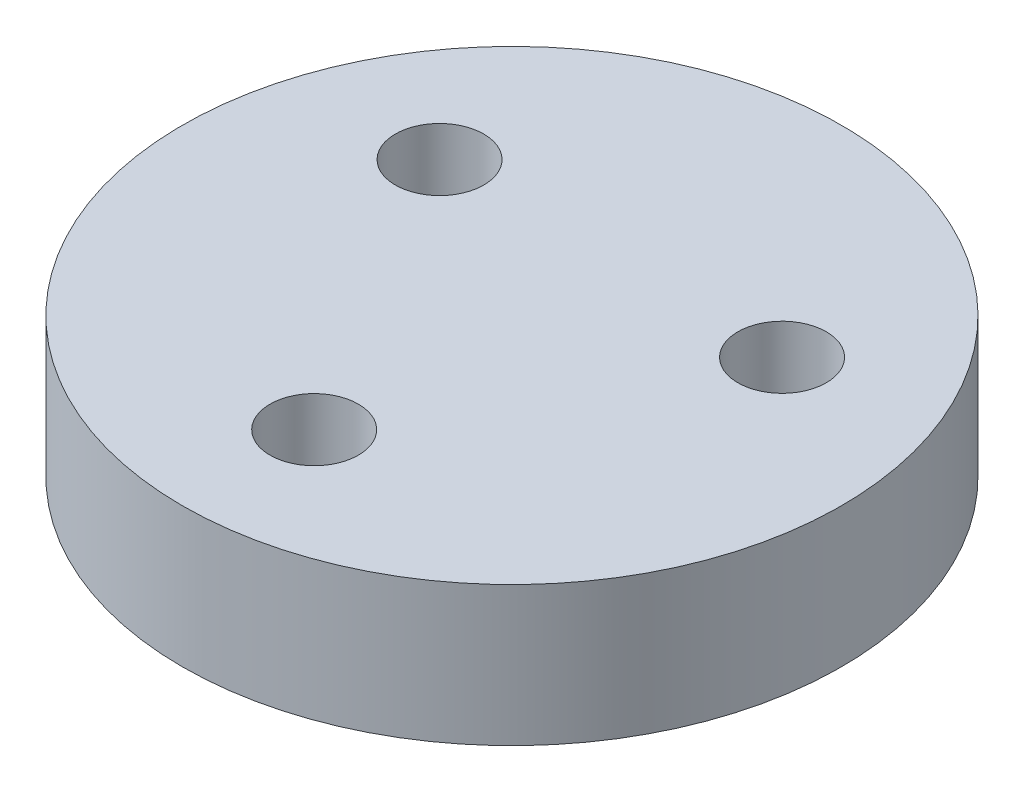
SolidWorks part; units mm, degrees
ref_plane "Front Plane" through (0, 0, 0) normal (0, 0, 1) x (1, 0, 0)
ref_plane "Top Plane" through (0, 0, 0) normal (0, 1, 0) x (1, 0, 0)
ref_plane "Right Plane" through (0, 0, 0) normal (1, 0, 0) x (0, 0, -1)
sketch "Sketch4" plane through (0, 0, 0) normal (0, 1, 0) x (1, 0, 0)
  circle A0 centre (0, 0) radius 30
  dimension "D1" = 60
extrude "Boss-Extrude2" add sketch "Sketch4" along normal blind 12.7
sketch "Sketch5" plane through (0, 0, 0) normal (0, -1, 0) x (1, 0, 0)
  circle A0 centre (0, 18) radius 4.025
  circle A1 centre (15.5885, -9) radius 4.025
  circle A2 centre (-15.5885, -9) radius 4.025
  point P10 (0, 0)
  dimension "D1" = 8.05
  dimension "D2" = 18
extrude "Cut-Extrude1" cut sketch "Sketch5" against normal blind 12.7
